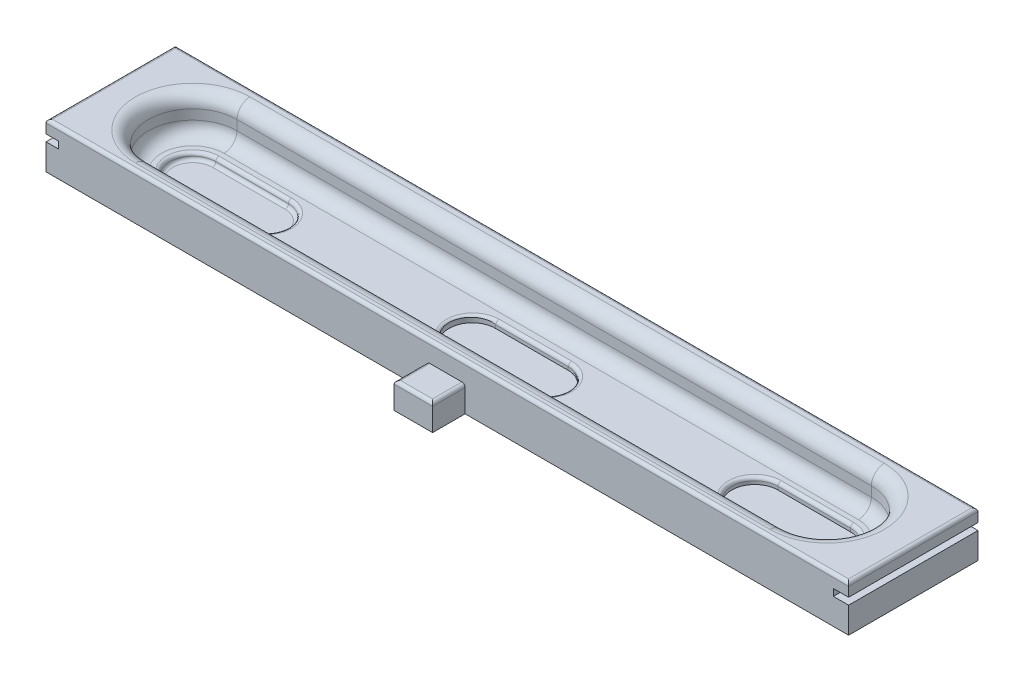
SolidWorks part; units mm, degrees
ref_plane "Front Plane" through (0, 0, 0) normal (0, 0, 1) x (1, 0, 0)
ref_plane "Top Plane" through (0, 0, 0) normal (0, 1, 0) x (1, 0, 0)
ref_plane "Right Plane" through (0, 0, 0) normal (1, 0, 0) x (0, 0, -1)
sketch "Sketch1" plane through (0, 0, 0) normal (0, 1, 0) x (1, 0, 0)
  line L2 (0.7909, -28.3198) -> (247.2909, -28.3198)
  line L4 (247.2909, 11.4134) -> (0.7909, 11.4134)
  line L6 (247.2909, 11.4134) -> (247.2909, -28.3198)
  line L7 (0.7909, 11.4134) -> (0.7909, -28.3198)
  dimension "D1" = 246.5
extrude "Boss-Extrude1" add sketch "Sketch1" along normal blind 14
sketch "Sketch3" plane through (0, 14, 0) normal (0, 1, 0) x (1, 0, 0)
  line L0 (37.1381, -19.9605) -> (-7.858, -19.9605) construction
  line L2 (37.1381, -19.9605) -> (37.1381, -24.4605) construction
  line L4 (37.1381, -19.9605) -> (123.1941, -19.9579) construction
  line L5 (123.6473, -19.9605) -> (210.1566, -19.9605) construction
  line L6 (210.1566, -19.9605) -> (210.1566, -24.4605) construction
  line L7 (123.6473, -19.9605) -> (123.6473, -24.4605) construction
  line L8 (37.1381, -19.9605) -> (37.1381, 7.1502) construction
  line L9 (123.6473, -19.9605) -> (123.6473, 8.5509) construction
  line L10 (210.1566, -19.9605) -> (210.1566, 7.8884) construction
  line L11 (0.0174, -19.9605) -> (247.1649, -19.9605)
  circle A2 centre (123.7727, -8.9393) radius 11.15
  circle A3 centre (37.3245, -8.6421) radius 11.15
  circle A4 centre (209.8985, -8.6813) radius 11.15
  dimension "D2" = 22.3
  dimension "D3" = 22.3
  dimension "D4" = 22.3
sketch "Sketch2" plane through (0, 0, 28.3198) normal (0, 0, 1) x (1, 0, 0)
  line L0 (0, 10.1) -> (0, 8)
  line L2 (0, 8) -> (4.6941, 8)
  line L3 (4.6941, 8) -> (4.6941, 10.1)
  line L5 (4.6941, 10.1) -> (0, 10.1)
extrude "Cut-Extrude1" cut sketch "Sketch2" against normal through all
sketch "Sketch4" plane through (0, 14, 0) normal (0, 1, 0) x (1, 0, 0)
sketch "Sketch5" plane through (0, 14, 0) normal (0, 1, 0) x (1, 0, 0)
  line L0 (26.1745, -8.6421) -> (221.0485, -8.6813) construction
  line L1 (26.1773, 4.9465) -> (221.0512, 4.9073)
  line L2 (26.1718, -22.2308) -> (221.0457, -22.27)
  circle A0 centre (37.3245, -8.6421) radius 11.15 construction
  circle A1 centre (209.8985, -8.6813) radius 11.15 construction
  arc A2 (26.1773, 4.9465) -> (26.1718, -22.2308) centre (26.1745, -8.6421) ccw
  arc A3 (221.0457, -22.27) -> (221.0512, 4.9073) centre (221.0485, -8.6813) ccw
  point P6 (123.6115, -8.6617)
extrude "Cut-Extrude3" cut sketch "Sketch5" against normal blind 11
fillet "Fillet2" radius 4 8 edges at (123.6088, 3, 22.2504) (234.6371, 3, 8.6841) (234.6371, 14, 8.6841) (12.5859, 3, 8.6394) (12.5859, 14, 8.6394) (123.6142, 3, -4.9269) (123.6142, 14, -4.9269) (123.6088, 14, 22.2504)
sketch "Sketch6" plane through (0, 3, 0) normal (0, 1, 0) x (1, 0, 0)
  line L0 (26.1745, -8.6421) -> (48.4745, -8.6421) construction
  line L1 (26.1745, -1.5442) -> (48.4745, -1.5442)
  line L2 (26.1745, -15.7401) -> (48.4745, -15.7401)
  line L3 (112.5783, -9.0257) -> (134.8783, -9.0257) construction
  line L4 (112.5783, -1.9278) -> (134.8783, -1.9278)
  line L5 (112.5783, -16.1237) -> (134.8783, -16.1237)
  circle A0 centre (37.3245, -8.6421) radius 11.15 construction
  arc A1 (26.1745, -1.5442) -> (26.1745, -15.7401) centre (26.1745, -8.6421) ccw
  arc A2 (48.4745, -15.7401) -> (48.4745, -1.5442) centre (48.4745, -8.6421) ccw
  arc A3 (112.5783, -1.9278) -> (112.5783, -16.1237) centre (112.5783, -9.0257) ccw
  arc A4 (134.8783, -16.1237) -> (134.8783, -1.9278) centre (134.8783, -9.0257) ccw
  point P4 (37.3245, -8.6421)
  point P11 (123.7283, -9.0257)
extrude "Cut-Extrude4" cut sketch "Sketch6" against normal blind 2
fillet "Fillet6" radius 1 16 edges at (19.0766, 3, 8.6421) (37.3245, 3, 1.5442) (55.5725, 3, 8.6421) (37.3245, 3, 15.7401) (37.3245, 1, 1.5442) (55.5725, 1, 8.6421) (37.3245, 1, 15.7401) (19.0766, 1, 8.6421) (105.4803, 3, 9.0257) (123.7283, 3, 1.9278) (141.9763, 3, 9.0257) (123.7283, 3, 16.1237) (123.7283, 1, 1.9278) (141.9763, 1, 9.0257) (123.7283, 1, 16.1237) (105.4803, 1, 9.0257)
ref_plane "Plane1" through (123.6473, 0, 0) normal (1, 0, 0) x (0, 0, -1)
mirror "Mirror4" about plane through (123.6473, 0, 0) normal (1, 0, 0) of "Cut-Extrude4"
fillet "Fillet8" radius 1 4 edges at (209.9701, 3, 15.7401) (228.2181, 3, 8.6421) (209.9701, 3, 1.5442) (191.7222, 3, 8.6421)
mirror "Mirror5" about plane through (123.6473, 0, 0) normal (1, 0, 0) of "Cut-Extrude1"
sketch "Sketch7" plane through (0, 0, 28.3198) normal (0, 0, 1) x (1, 0, 0)
  line L0 (123.5912, 14) -> (123.6473, 0) construction
  line L1 (0.0174, 14) -> (247.1649, 14) construction
  line L2 (0.7909, 0) -> (247.2909, 0) construction
  line L3 (123.6473, -7.7) -> (123.6473, 7.7) construction
  line L9 (117.7248, 7.9809) -> (129.5137, 6.0191) construction
  line L10 (117.7248, 6.0191) -> (129.5137, 7.9809) construction
  line L11 (117.7248, 0) -> (129.5137, 0)
  line L12 (117.7248, 0) -> (117.7248, 7.9809)
  line L13 (117.7248, 7.9809) -> (129.5137, 7.9809)
  line L14 (129.5137, 0) -> (129.5137, 7.9809)
  point P8 (123.6193, 7)
extrude "Boss-Extrude2" add sketch "Sketch7" along normal blind 10
fillet "Fillet7" radius 1 7 edges at (124.0409, 14, 28.3198) (124.0409, 14, -11.4134) (247.2909, 14, 8.4532) (0.7909, 14, 8.4532) (129.5137, 7.9809, 33.3198) (123.6193, 7.9809, 38.3198) (117.7248, 7.9809, 33.3198)
